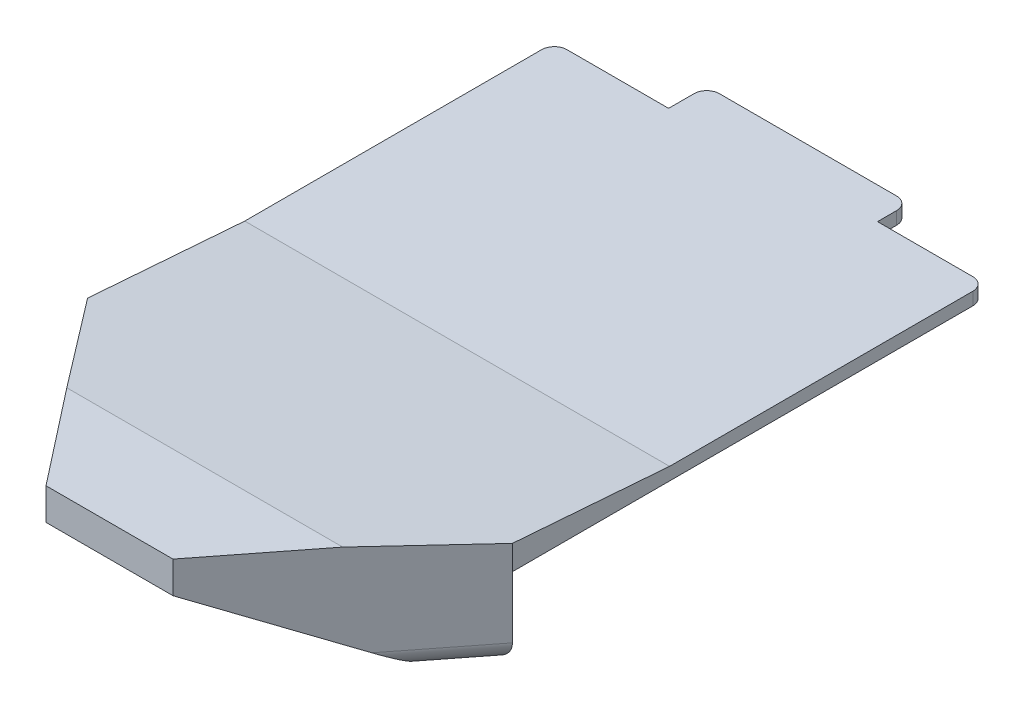
SolidWorks part; units mm, degrees
ref_plane "Front Plane" through (0, 0, 0) normal (0, 0, 1) x (1, 0, 0)
ref_plane "Top Plane" through (0, 0, 0) normal (0, 1, 0) x (1, 0, 0)
ref_plane "Right Plane" through (0, 0, 0) normal (1, 0, 0) x (0, 0, -1)
sketch "Sketch1" plane through (0, 0, 0) normal (0, 1, 0) x (1, 0, 0)
  line L0 (0, 0) -> (-16.35, 0)
  line L1 (-16.35, 0) -> (-16.35, -9.85)
  line L2 (-16.35, -9.85) -> (-2.6, -9.85)
  line L3 (-20.1, -33) -> (-20.1, -75)
  line L4 (-20.1, -75) -> (0, -75)
  line L5 (0, -75) -> (0, 0)
  line L6 (-2.6, -9.85) -> (-2.6, -33)
  line L7 (-2.6, -33) -> (-20.1, -33)
  dimension "D1" = 16.35
  dimension "D2" = 9.85
  dimension "D3" = 13.75
  dimension "D4" = 3.75
  dimension "D5" = 23.15
  dimension "D6" = 42
extrude "Boss-Extrude1" add sketch "Sketch1" along normal blind 7.7
sketch "Sketch2" plane through (0, 0, 75) normal (0, 0, 1) x (1, 0, 0)
  line L0 (-20.1, 7.7) -> (-20.1, 0) construction
  line L1 (-20.1, 5.1) -> (-13.1, 5.1)
  line L2 (-20.1, 5.1) -> (-20.1, 2)
  line L3 (-20.1, 2) -> (-13.1, 2)
  line L4 (-13.1, 5.1) -> (-13.1, 2)
  line L5 (-20.1, 0) -> (0, 0) construction
  dimension "D1" = 7
  dimension "D2" = 3.1
  dimension "D3" = 2
extrude "Cut-Extrude1" cut sketch "Sketch2" against normal through all
fillet "Fillet1" radius 10 1 edges at (-2.6, 3.85, 33)
sketch "Sketch3" plane through (0, 7.7, 0) normal (0, 1, 0) x (1, 0, 0)
  line L0 (0, 0) -> (0, -75)
  line L1 (0, -75) -> (-33.45, -75)
  line L2 (-33.45, -75) -> (-33.45, 0)
  line L3 (-33.45, 0) -> (0, 0)
  line L4 (0, -75) -> (0, -105)
  line L5 (0, -105) -> (-10, -105)
  line L6 (0, 0) -> (0, 4.5)
  line L7 (-33.45, -75) -> (-10, -105)
  line L8 (0, 4.5) -> (-33.45, 4.5)
  line L9 (-33.45, 4.5) -> (-33.45, 0)
  line M7 (0, -75) -> (0, 0)
  line M8 (0, 0) -> (-16.35, 0)
  line M9 (-16.35, 0) -> (-16.35, -9.85)
  line M10 (-16.35, -9.85) -> (-2.6, -9.85)
  line M11 (-2.6, -9.85) -> (-2.6, -23)
  arc M12 (-2.6, -23) -> (-12.6, -33) centre (-12.6, -23) cw
  line M13 (-12.6, -33) -> (-20.1, -33)
  line M14 (-20.1, -33) -> (-20.1, -75)
  line M15 (-20.1, -75) -> (0, -75)
  dimension "D1" = 33.45
  dimension "D2" = 30
  dimension "D3" = 10
  dimension "D4" = 4.5
extrude "Boss-Extrude2" add sketch "Sketch3" along normal blind 2 contours M15 M7 M8 M9 M10 M11 M12 M13 M14 | L3 L2 L1 M14 M13 M12 M11 M10 M9 | L5 L4 L1 M15 | L3 M8 region at (-9.1846, 7.7, 44.4658) region at (-16.725, 7.7, -2.25) region at (-11.9172, 7.7, 87.3015) region at (-22.489, 7.7, 32.1752)
sketch "Sketch4" plane through (0, 0, 0) normal (1, 0, 0) x (0, 0, -1)
  line L0 (-105, 9.7) -> (-105, 12.7)
  line L1 (-105, 12.7) -> (-90, 12.7)
  line L2 (-90, 12.7) -> (-50.25, 9.7)
  line L3 (-105, 9.7) -> (4.5, 9.7) construction
  line L4 (-105, 9.7) -> (-50.25, 9.7)
  point P8 (-50.25, 9.7)
  dimension "D1" = 15
  dimension "D2" = 3
extrude "Boss-Extrude3" add sketch "Sketch4" against normal up to surface (33.45 mm away) up to face at (-33.45, 8.7, 35.25)
sketch "Sketch5" plane through (-33.45, 0, 0) normal (-1, 0, 0) x (0, 0, 1)
  line L0 (75, 7.7) -> (75, -5)
  line L1 (75, -5) -> (82, -5)
  line L2 (82, -5) -> (105, 7.7)
  line L3 (105, 7.7) -> (75, 7.7)
  line L4 (33, 0) -> (75, 0) construction
  dimension "D1" = 5
  dimension "D2" = 7
extrude "Boss-Extrude4" add sketch "Sketch5" against normal up to surface (33.45 mm away) up to face at (0, 7.56, 49.125)
sketch "Sketch6" plane through (0, 7.7, 0) normal (0, 1, 0) x (1, 0, 0)
  line L0 (-33.45, -75) -> (-10, -105)
  line L1 (-10, -105) -> (-33.45, -105)
  line L2 (-33.45, -105) -> (-33.45, -75)
extrude "Cut-Extrude2" cut sketch "Sketch6" against normal through all both and the other way through all
sketch "Sketch7" plane through (0, 0, 0) normal (1, 0, 0) x (0, 0, -1)
  line L0 (-75, 0) -> (-85, 0)
  line L1 (-85, 0) -> (-80, -5)
  line L2 (-82, -5) -> (-75, -5) construction
  line L3 (-80, -5) -> (-75, -5)
  line L4 (-75, -5) -> (-75, 0)
  dimension "D1" = 5
  dimension "D2" = 10
extrude "Cut-Extrude3" cut sketch "Sketch7" against normal blind 10
fillet "Fillet3" radius 1 2 edges at (-5, -5, 80) (-10, -5, 77.5)
fillet "Fillet4" [suppressed] radius 5
mirror "Mirror1" about plane through (0, 7.7, 75) normal (-1, 0, 0) of bodies 110
fillet "Fillet5" radius 3 2 edges at (-30.7142, -5, 78.5) (30.7142, -5, 78.5)
sketch "Sketch8" plane through (0, 9.7, 0) normal (0, 1, 0) x (1, 0, 0)
  line L0 (33.45, 4.5) -> (33.45, -0.5)
  line L1 (33.45, -50.25) -> (33.45, 4.5) construction
  line L2 (33.45, -0.5) -> (16.45, -0.5)
  line L3 (16.45, -0.5) -> (16.45, 4.5)
  line L4 (33.45, 4.5) -> (-33.45, 4.5) construction
  line L5 (16.45, 4.5) -> (33.45, 4.5)
  line L6 (0, 37.0905) -> (0, -37.0905) construction
  line L7 (-16.45, -0.5) -> (-16.45, 4.5) construction
  line L8 (-33.45, -0.5) -> (-16.45, -0.5) construction
  line L9 (-33.45, 4.5) -> (-33.45, -0.5) construction
  line L10 (-16.45, 4.5) -> (-33.45, 4.5) construction
  line L11 (-15.45, -1.5) -> (-15.45, 5.5)
  line L12 (-15.45, 5.5) -> (-34.45, 5.5)
  line L13 (-34.45, 5.5) -> (-34.45, -1.5)
  line L14 (-34.45, -1.5) -> (-15.45, -1.5)
  point P13 (0, 0)
  dimension "D1" = 5
  dimension "D2" = 17
  dimension "D3" = 1
extrude "Cut-Extrude4" cut sketch "Sketch8" against normal up to surface (9.7 mm away) up to face at (0, 0, 38.419)
fillet "Fillet6" radius 2 2 edges at (-15.45, 8.7, -4.5) (-33.45, 8.7, 1.5)
fillet "Fillet7" radius 2 2 edges at (33.45, 8.7, 0.5) (16.45, 8.7, -4.5)
